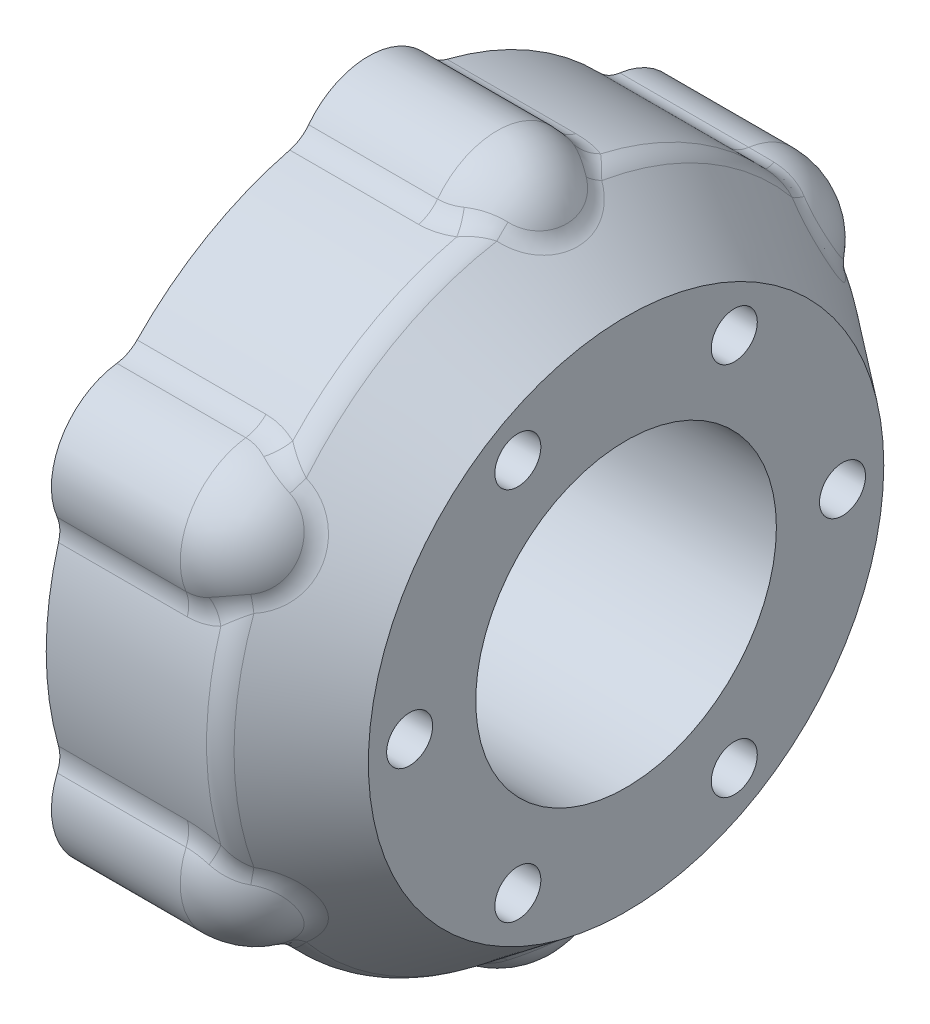
SolidWorks part; units mm, degrees
material "PET"
ref_plane "Front" through (0, 0, 0) normal (0, 0, 1) x (1, 0, 0)
ref_plane "Top" through (0, 0, 0) normal (0, 1, 0) x (1, 0, 0)
ref_plane "Right" through (0, 0, 0) normal (1, 0, 0) x (0, 0, -1)
sketch "Sketch1" plane through (0, 0, 0) normal (0, 0, 1) x (1, 0, 0)
  line L0 (0, 23.8125) -> (0, 11.1125)
  line L3 (0, 11.1125) -> (19.05, 11.1125)
  line L4 (19.05, 11.1125) -> (19.05, 19.05)
  line L5 (19.05, 19.05) -> (13.3773, 23.3045)
  line L6 (11.8533, 23.8125) -> (0, 23.8125)
  line L7 (0, 0) -> (-10.95, 0) construction
  arc A0 (13.3773, 23.3045) -> (11.8533, 23.8125) centre (11.8533, 21.2725) ccw
  point P12 (12.7, 23.8125)
  dimension "D8" = 2.54
  dimension "D2" = 47.625
  dimension "D3" = 38.1
  dimension "D4" = 12.7
  dimension "D5" = 19.05
  dimension "D7" = 22.225
revolve "Revolve1" add sketch "Sketch1" angle 360 about L7
sketch "Sketch2" plane through (0, 0, 0) normal (0, 1, 0) x (1, 0, 0)
  line L0 (0, 0) -> (24.0323, 0) construction
  line L1 (19.05, 16) -> (23.214, 16) construction
  line L2 (19.05, -19.05) -> (19.05, 19.05) construction
  line L3 (19.05, 16) -> (0, 16)
  line L4 (0, 23.8125) -> (0, -23.8125) construction
  line L5 (0, 16) -> (0, 19.25)
  line L6 (0, 19.25) -> (12.7, 19.25)
  line L7 (12.7, 19.25) -> (12.7, 17.7)
  line L8 (12.7, 17.7) -> (19.05, 17.7)
  line L9 (19.05, 17.7) -> (19.05, 16)
  dimension "D1" = 3.4
  dimension "D2" = 6.5
  dimension "D3" = 6.35
  dimension "D4" = 32
revolve "Cut-Revolve1" cut sketch "Sketch2" angle 360 about L1
sketch "Sketch3" plane through (0, 0, 0) normal (0, 0, 1) x (1, 0, 0)
  line L0 (0, 20.6375) -> (15.0813, 20.6375)
  line L1 (0, 23.8125) -> (0, -23.8125) construction
  line L3 (9.525, 26.1938) -> (0, 26.1938)
  line L4 (0, 26.1938) -> (0, 20.6375)
  line L5 (0, 20.6375) -> (-4.5359, 20.6375) construction
  line L6 (0, 0) -> (8.7066, 0) construction
  arc A0 (9.525, 26.1938) -> (15.0813, 20.6375) centre (9.525, 20.6375) cw
  dimension "D1" = 11.1125
  dimension "D3" = 41.275
  dimension "D4" = 9.525
revolve "Revolve2" add sketch "Sketch3" angle 360 about L5
sketch "Sketch6" plane through (0, 0, 0) normal (-1, 0, 0) x (0, 0, 1)
  point P0 (0, 20.6375)
hole_wizard "1/4 (0.25) Diameter Hole1" positions "Sketch6" profile "Sketch5" hole size "1/4" standard "ANSI Inch"
sketch "Sketch5" plane through (0, 20.6375, 0) normal (0, 1, 0) x (0, 0, 1)
  line L0 (0, 0) -> (0, 11.4327)
  line L1 (0, 11.4327) -> (3.175, 9.525)
  line L2 (3.175, 9.525) -> (3.175, 0)
  line L5 (3.175, 0) -> (0, 0)
  line L10 (0, 11.4327) -> (-3.175, 9.525) construction
  line L11 (0, -6.35) -> (0, 107.95) construction
  dimension "Hole Dia." = 6.35
  dimension "Hole Depth" = 9.525
  dimension "Drill Angle" = 118
fillet "Fillet1" radius 2.54 7 edges at (10.5195, 23.3327, -4.7559) (10.9537, 23.3582, 4.6291) (14.8568, 22.1945, 0.1413) (4.7625, 23.3088, -4.872) (4.7625, 23.3088, 4.872) (12.5596, 23.4166, -3.7337) (12.9262, 23.3161, 3.4826)
pattern_circular "CirPattern1" count 6 over 360 about axis through (0, 0, 0) along (1, 0, 0) of "Cut-Revolve1", "1/4 (0.25) Diameter Hole1", "Revolve2", "Fillet1"
